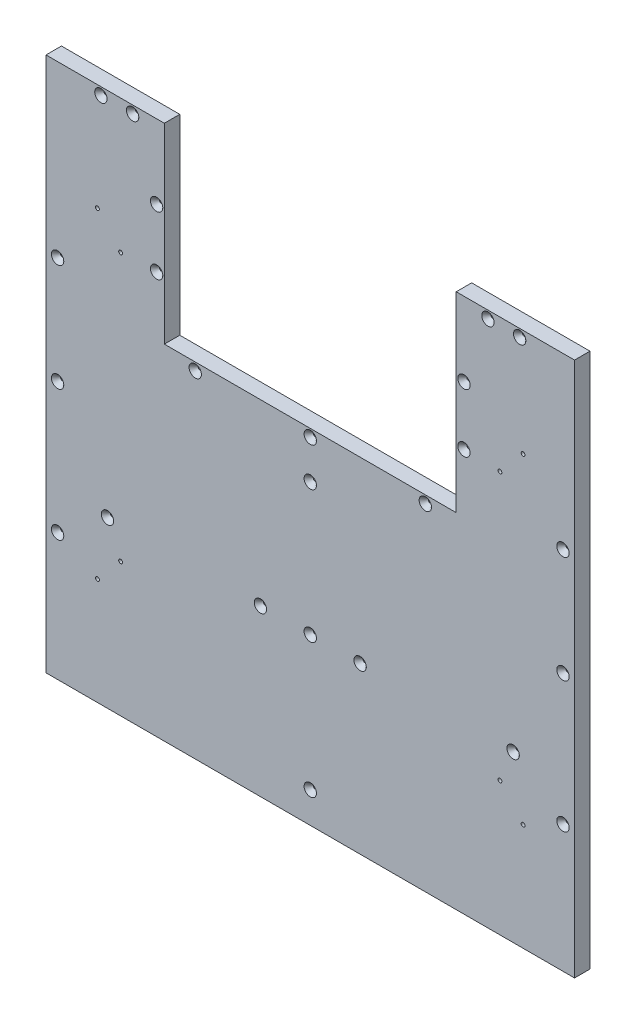
SolidWorks part; units mm, degrees
material "Beech"
ref_plane "Front Plane" through (0, 0, 0) normal (0, 0, 1) x (1, 0, 0)
ref_plane "Top Plane" through (0, 0, 0) normal (0, 1, 0) x (1, 0, 0)
ref_plane "Right Plane" through (0, 0, 0) normal (1, 0, 0) x (0, 0, -1)
sketch "Sketch1" plane through (0, 0, 0) normal (0, 0, 1) x (1, 0, 0)
  line L0 (341.3045, 12.7) -> (244.0045, 12.7)
  line L2 (341.3045, 12.7) -> (244.0045, 12.7) construction
  line L3 (244.0045, 12.7) -> (244.0045, -144.6)
  line L4 (244.0045, -144.6) -> (124.0045, -144.6)
  line L5 (341.3045, -455.5295) -> (-93.2955, -455.5295) construction
  line L6 (124.0045, -144.6) -> (124.0045, -427.3421)
  line L7 (124.0045, -427.3421) -> (341.3045, -427.3421)
  line L8 (341.3045, -427.3421) -> (341.3045, 12.7)
  line L12 (16.7045, -144.6) -> (231.3045, -144.6) construction
  point P18 (124.0045, -144.6)
  dimension "D1" = 28.1874
extrude "Boss-Extrude1" add sketch "Sketch1" along normal blind 12.7
mirror "Mirror1" about plane through (124.0045, -144.6, 12.7) normal (1, 0, 0) of "Boss-Extrude1"
hole_wizard "Hole1" positions "Sketch2" profile "Sketch3" legacy
sketch "Sketch2" plane through (124.0045, 10.4243, 12.7) normal (0, 0, 1) x (-1, 0, 0)
  line L12 (0, 0) -> (0, 155.0243) construction
  point P0 (-207.775, 333.0214)
  point P3 (-207.775, 225.489)
  point P6 (-207.775, 137.4243)
  point P9 (-172.1667, 4.0743)
  point P12 (-146.0833, 4.0743)
  point P15 (-94.6, 161.3743)
  point P18 (0, 161.3743)
  point P21 (94.6, 161.3743)
  point P24 (146.0833, 4.0743)
  point P27 (172.1667, 4.0743)
  point P30 (207.775, 137.4243)
  point P33 (207.775, 225.489)
  point P36 (207.775, 333.0214)
  point P39 (166.7958, 301.9704)
  point P42 (40.9792, 301.9704)
  point P45 (-40.9792, 301.9704)
  point P48 (-166.7958, 301.9704)
  point P51 (0, 193.1243)
  point P54 (0, 301.9704)
  point P57 (0, 412.3664)
  point P80 (-126.35, 106.8243)
  point P82 (-126.35, 58.6243)
  point P96 (126.35, 58.6243)
  point P97 (126.35, 106.8243)
sketch "Sketch3" plane through (331.7795, -322.5971, 12.7) normal (1, 0, 0) x (0, -1, 0)
  line L0 (0, 0) -> (0, 32.7039)
  line L1 (0, 32.7039) -> (1.5875, 31.75)
  line L2 (1.5875, 31.75) -> (1.5875, 4.0177)
  line L3 (1.5875, 4.0177) -> (5.08, 0)
  line L4 (5.08, 0) -> (0, 0)
  line L5 (0, -14.3089) -> (0, 102.4216) construction
  line L6 (0, 32.7039) -> (-1.5875, 31.75) construction
  line L7 (-1.5875, 4.0177) -> (-5.08, 0) construction
  dimension "Diameter" = 3.175
  dimension "Depth" = 31.75
  dimension "C-Sink Diameter" = 10.16
  dimension "C-Sink Angle" = 82
  dimension "Drill Angle" = 118
hole_wizard "Hole2" positions "Sketch4" profile "Sketch5" legacy
sketch "Sketch4" plane through (124.0045, 10.4243, 0) normal (0, 0, -1) x (1, 0, 0)
  line L8 (155.95, -2.2757) -> (155.95, 437.7664) construction
  line L11 (175, -2.2757) -> (175, 437.7664) construction
  line L15 (155.95, -2.2757) -> (155.95, 107.7348)
  line L16 (155.95, 107.7348) -> (155.95, 217.7454)
  line L17 (155.95, 217.7454) -> (155.95, 327.7559)
  line L18 (155.95, 327.7559) -> (155.95, 437.7664)
  line L20 (175, -2.2757) -> (175, 85.7327)
  line L21 (175, 85.7327) -> (175, 173.7411)
  line L22 (175, 173.7411) -> (175, 261.7496)
  line L23 (175, 261.7496) -> (175, 349.758)
  line L24 (175, 349.758) -> (175, 437.7664)
  line L25 (0, 155.0243) -> (0, 437.7664) construction
  point P36 (155.95, 107.7348)
  point P40 (155.95, 327.7559)
  point P46 (175, 85.7327)
  point P52 (175, 349.758)
  point P77 (-175, 349.758)
  point P80 (-175, 85.7327)
  point P81 (-155.95, 327.7559)
  point P83 (-155.95, 107.7348)
sketch "Sketch5" plane through (-31.9455, -97.3105, 0) normal (1, 0, 0) x (0, 1, 0)
  line L0 (0, 0) -> (0, 32.7039)
  line L1 (0, 32.7039) -> (1.5875, 31.75)
  line L2 (1.5875, 31.75) -> (1.5875, 4.0177)
  line L3 (1.5875, 4.0177) -> (5.08, 0)
  line L4 (5.08, 0) -> (0, 0)
  line L5 (0, -14.3089) -> (0, 102.4216) construction
  line L6 (0, 32.7039) -> (-1.5875, 31.75) construction
  line L7 (-1.5875, 4.0177) -> (-5.08, 0) construction
  dimension "Diameter" = 3.175
  dimension "Depth" = 31.75
  dimension "C-Sink Diameter" = 10.16
  dimension "C-Sink Angle" = 82
  dimension "Drill Angle" = 118
